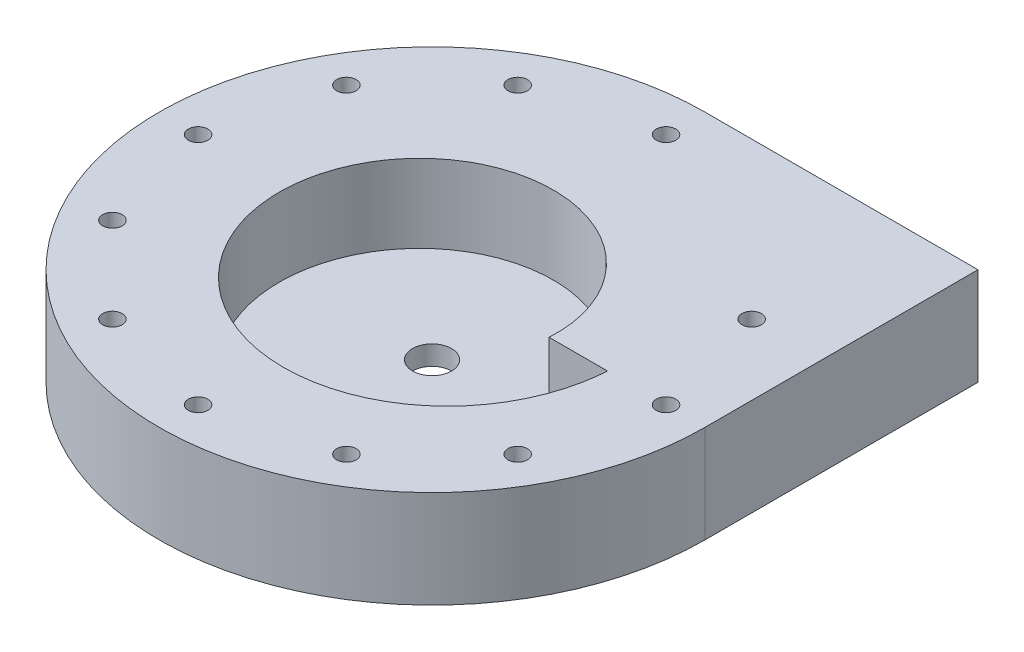
SolidWorks part; units mm, degrees
material "AISI 316 Annealed Stainless Steel Bar (SS)"
ref_plane "Front Plane" through (0, 0, 0) normal (0, 0, 1) x (1, 0, 0)
ref_plane "Top Plane" through (0, 0, 0) normal (0, 1, 0) x (1, 0, 0)
ref_plane "Right Plane" through (0, 0, 0) normal (1, 0, 0) x (0, 0, -1)
sketch "Sketch1" plane through (0, 0, 0) normal (0, 1, 0) x (1, 0, 0)
  line L0 (0, 0) -> (38.1, 0) construction
  line L1 (38.1, 0) -> (57.15, 0)
  line L2 (88.9, 0) -> (88.9, 88.9)
  line L3 (88.9, 88.9) -> (6.35, 88.9)
  line L4 (6.35, 88.9) -> (6.35, 88.6729)
  line L5 (47.625, 0) -> (47.625, 88.9) construction
  line L6 (6.35, 88.9) -> (0, 88.9)
  circle A0 centre (0, 0) radius 88.9
  circle A1 centre (0, 0) radius 6.35
  spline S0 degree 4 poles (29.5988, -21.5048) (29.8351, -21.22) (30.3001, -20.6441) (31.4238, -19.1734) (32.8568, -17.0118) (34.113, -14.7413) (35.1815, -12.3857) (35.8524, -10.6726) (36.3326, -9.2894) (36.7571, -7.8938) (37.0811, -6.6592) (37.3245, -5.5927) (37.5045, -4.6991) (37.6346, -3.9817) (37.751, -3.2617) (37.8534, -2.5399) (37.9255, -1.9518) (37.9744, -1.4973) (38.0054, -1.1831) (38.0222, -1.0035) (38.0424, -0.7748) (38.0658, -0.4876) (38.0909, -0.144) (38.1067, 0.0986) (38.1262, 0.4409) (38.1426, 0.7716) (38.158, 1.1548) (38.1712, 1.6096) (38.1802, 2.1518) (38.1802, 2.7648) (38.168, 3.5342) (38.1337, 4.4555) (38.065, 5.5299) (37.9473, 6.754) (37.7908, 7.9741) (37.5955, 9.1885) (37.3618, 10.3961) (37.0901, 11.5957) (36.7806, 12.7861) (36.2602, 14.5562) (35.4433, 16.878) (34.0888, 19.9822) (31.9638, 23.7352) (29.245, 27.4747) (25.8787, 31.0784) (22.0997, 34.2465) (18.4833, 36.5997) (14.6541, 38.5785) (11.22, 39.9409) (8.2776, 40.8467) (4.6752, 41.6527) (1.018, 42.1752) (-3.2917, 42.3676) (-8.2093, 42.0167) (-14.2651, 40.8758) (-21.2611, 38.4151) (-28.7662, 34.0526) (-35.122, 28.1428) (-39.5416, 22.1915) (-43.0486, 15.6831) (-45.6523, 8.5647) (-47.131, -0.1568) (-46.6549, -10.2288) (-44.0713, -19.9682) (-39.6379, -28.8272) (-33.5183, -36.6152) (-25.9784, -43.0353) (-17.3298, -47.8558) (-7.9143, -50.9141) (1.9103, -52.1192) (10.5502, -51.5343) (17.7692, -49.8909) (23.5588, -47.7937) (28.0161, -45.6963) (32.2624, -43.1995) (36.2636, -40.3263) (39.9882, -37.1026) (43.4074, -33.5568) (46.8815, -29.2396) (50.2256, -24.0643) (52.9395, -18.5267) (54.9867, -12.7154) (56.0714, -8.2271) (56.5719, -5.3479) (56.8158, -3.5193) (56.9065, -2.756) (56.9641, -2.2218) (57.0097, -1.76) (57.0445, -1.3812) (57.0705, -1.0803) (57.1017, -0.693) (57.1384, -0.1834) (57.1557, 0.0791) (57.18, 0.4966) (57.1965, 0.8062) (57.2081, 1.0431) (57.2182, 1.2727) (57.2273, 1.5007) (57.2418, 1.9027) (57.255, 2.3672) (57.2647, 2.8861) (57.2703, 3.5797) (57.2684, 4.2729) (57.2554, 5.0818) (57.2258, 6.0057) (57.1813, 6.9291) (57.122, 7.8517) (56.9554, 9.9251) (56.4457, 14.0562) (55.515, 18.3598) (54.112, 22.7722) (52.7365, 26.2052) (52.1806, 27.4758) (51.7925, 28.3148) (51.5941, 28.7323) knots 0 0 0 0 0 0.004243 0.008485 0.021213 0.029698 0.033941 0.03812 0.0423 0.04648 0.05066 0.052749 0.054839 0.056929 0.059019 0.061109 0.063199 0.063721 0.064244 0.064766 0.065289 0.066334 0.067379 0.06826 0.069141 0.070022 0.070903 0.072666 0.074428 0.07619 0.077953 0.081477 0.085002 0.088527 0.092051 0.095576 0.099101 0.102625 0.10615 0.109675 0.120249 0.130823 0.144922 0.15902 0.173119 0.187218 0.201317 0.208366 0.222465 0.229514 0.236563 0.250662 0.264761 0.27886 0.292959 0.321156 0.349353 0.377551 0.39165 0.405748 0.433946 0.464057 0.492254 0.520452 0.548649 0.576847 0.605044 0.633242 0.661439 0.689636 0.717834 0.731933 0.746031 0.76013 0.774229 0.788328 0.802426 0.816525 0.830624 0.851772 0.87292 0.887019 0.901118 0.904642 0.906405 0.908167 0.909929 0.91081 0.911692 0.912573 0.913454 0.915216 0.916541 0.917203 0.917866 0.918528 0.919191 0.919853 0.920515 0.923165 0.92449 0.925814 0.928464 0.931113 0.933763 0.936412 0.939062 0.941711 0.957608 0.984103 0.989402 0.994701 1 1 1 1 1 construction
  spline S1 degree 4 poles (38.1, 0) (38.1042, 0.065) (38.1122, 0.1956) (38.1262, 0.4409) (38.1426, 0.7716) (38.158, 1.1548) (38.1712, 1.6096) (38.1802, 2.1518) (38.1802, 2.7648) (38.168, 3.5342) (38.1337, 4.4555) (38.065, 5.5299) (37.9473, 6.754) (37.7908, 7.9741) (37.5955, 9.1885) (37.3618, 10.3961) (37.0901, 11.5957) (36.7806, 12.7861) (36.2602, 14.5562) (35.4433, 16.878) (34.0888, 19.9822) (31.9638, 23.7352) (29.245, 27.4747) (25.8787, 31.0784) (22.0997, 34.2465) (18.4833, 36.5997) (14.6541, 38.5785) (11.22, 39.9409) (8.2776, 40.8467) (4.6752, 41.6527) (1.018, 42.1752) (-3.2917, 42.3676) (-8.2093, 42.0167) (-14.2651, 40.8758) (-21.2611, 38.4151) (-28.7662, 34.0526) (-35.122, 28.1428) (-39.5416, 22.1915) (-43.0486, 15.6831) (-45.6523, 8.5647) (-47.131, -0.1568) (-46.6549, -10.2288) (-44.0713, -19.9682) (-39.6379, -28.8272) (-33.5183, -36.6152) (-25.9784, -43.0353) (-17.3298, -47.8558) (-7.9143, -50.9141) (1.9103, -52.1192) (10.5502, -51.5343) (17.7692, -49.8909) (23.5588, -47.7937) (28.0161, -45.6963) (32.2624, -43.1995) (36.2636, -40.3263) (39.9882, -37.1026) (43.4074, -33.5568) (46.8815, -29.2396) (50.2256, -24.0643) (52.9395, -18.5267) (54.9867, -12.7154) (56.0714, -8.2271) (56.5719, -5.3479) (56.8158, -3.5193) (56.9065, -2.756) (56.9641, -2.2218) (57.0097, -1.76) (57.0445, -1.3812) (57.0705, -1.0803) (57.1017, -0.693) (57.1284, -0.3226) (57.1416, -0.1301) (57.15, 0) knots 0.067379 0.067379 0.067379 0.067379 0.067379 0.06826 0.069141 0.070022 0.070903 0.072666 0.074428 0.07619 0.077953 0.081477 0.085002 0.088527 0.092051 0.095576 0.099101 0.102625 0.10615 0.109675 0.120249 0.130823 0.144922 0.15902 0.173119 0.187218 0.201317 0.208366 0.222465 0.229514 0.236563 0.250662 0.264761 0.27886 0.292959 0.321156 0.349353 0.377551 0.39165 0.405748 0.433946 0.464057 0.492254 0.520452 0.548649 0.576847 0.605044 0.633242 0.661439 0.689636 0.717834 0.731933 0.746031 0.76013 0.774229 0.788328 0.802426 0.816525 0.830624 0.851772 0.87292 0.887019 0.901118 0.904642 0.906405 0.908167 0.909929 0.91081 0.911692 0.912573 0.913454 0.915216 0.915216 0.915216 0.915216 0.915216
  dimension "D1" = 177.8
  dimension "D4" = 12.7
  dimension "D2" = 38.1
extrude "Boss-Extrude1" add sketch "Sketch1" against normal blind 31.75 contours L1 S1 | A0 S1 L1 | A0 L2 L3 L4 | A0 L4 L6 region at (47.625, 0, 1.4012) region at (69.0608, 0, -69.037) region at (-61.0838, 0, 61.0838) region at (4.7629, 0, -88.8319)
extrude "Cut-Extrude1" cut sketch "Sketch1<3>" against normal blind 25.4 contours L1 S1 region at (47.625, 0, 1.4012)
sketch "Sketch1<3>" plane through (0, 0, 0) normal (0, 1, 0) x (1, 0, 0) same geometry as "Sketch1"
sketch "Sketch2" plane through (0, 0, 0) normal (0, 0, 1) x (1, 0, 0)
  line L3 (38.1, -25.4) -> (57.15, -25.4) construction
  line L4 (57.15, -25.4) -> (57.15, 0) construction
  circle A0 centre (49.2125, -17.4625) radius 7.9375
  dimension "D1" = 15.875
extrude "Cut-Extrude3" cut sketch "Sketch2" against normal through all
hole_wizard "1/4 (0.25) Diameter Hole1" positions "3DSketch2" profile "Sketch3" hole size "1/4" standard "ANSI Inch"
sketch3d "3DSketch2"
  line L2 (76.2, 0, 0) -> (0, 0, 0) construction
  point P0 (76.2, 0, 0)
  dimension "D1" = 76.2
sketch "Sketch3" plane through (76.2, 0, 0) normal (1, 0, 0) x (0, 0, 1)
  line L0 (0, 0) -> (0, 78.1077)
  line L1 (0, 78.1077) -> (3.175, 76.2)
  line L2 (3.175, 76.2) -> (3.175, 0)
  line L5 (3.175, 0) -> (0, 0)
  line L10 (0, 78.1077) -> (-3.175, 76.2) construction
  line L11 (0, -6.35) -> (0, 107.95) construction
  dimension "Hole Dia." = 6.35
  dimension "Hole Depth" = 76.2
  dimension "Drill Angle" = 118
pattern_circular "CirPattern1" count 12 over 360 about axis through (0, -31.75, 0) along (0, 1, 0) skipping 2 of "1/4 (0.25) Diameter Hole1"
equation "\"Volute IR\"= 1.5"
equation "\"Volute OR\"= 1.5 + 3 / 4"
equation "\"D2@Sketch1\"=\"Volute IR\""
